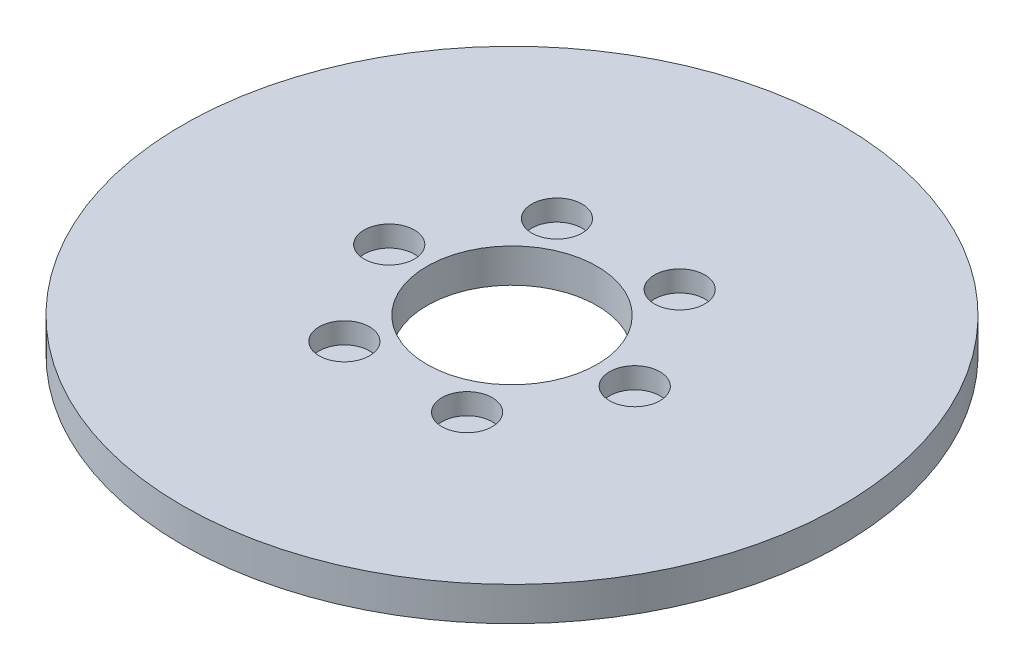
SolidWorks part; units mm, degrees
ref_plane "Front Plane" through (0, 0, 0) normal (0, 0, 1) x (1, 0, 0)
ref_plane "Top Plane" through (0, 0, 0) normal (0, 1, 0) x (1, 0, 0)
ref_plane "Right Plane" through (0, 0, 0) normal (1, 0, 0) x (0, 0, -1)
sketch "Sketch1" plane through (0, 0, 0) normal (0, 1, 0) x (1, 0, 0)
  circle A0 centre (0, 0) radius 77.5
  dimension "FLANGE_OD" = 155
extrude "Boss-Extrude1" add sketch "Sketch1" along normal blind 8
sketch "Sketch2" plane through (0, 0, 0) normal (0, 1, 0) x (1, 0, 0)
  circle A0 centre (0, 0) radius 20
  dimension "BORE_D" = 40
extrude "Cut-Extrude1" cut sketch "Sketch2" along normal through all
sketch "Sketch3" plane through (0, 8, 0) normal (0, 1, 0) x (1, 0, 0)
  circle A0 centre (0, 0) radius 28.8641 construction
  circle A1 centre (-28.8641, 0) radius 5.9224
  dimension "BOLT_D" = 11.8448
  dimension "BOLT_PCD" = 57.7282
extrude "Cut-Extrude2" cut sketch "Sketch3" against normal blind 4.917
pattern_circular "CirPattern1" count 6 over 360 about axis through (0, 0, 0) along (0, 1, 0) of "Cut-Extrude2"
